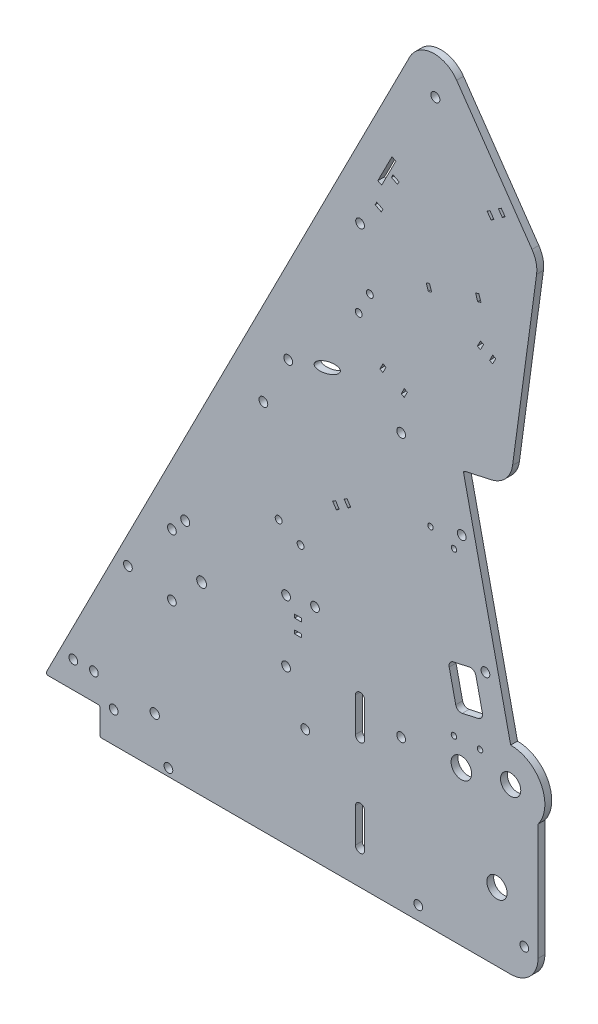
SolidWorks part; units mm, degrees
other "Markup1"
sketch "Sketch5"
ref_plane "Front Plane" through (0, 0, 0) normal (0, 0, 1) x (1, 0, 0)
ref_plane "Top Plane" through (0, 0, 0) normal (0, 1, 0) x (1, 0, 0)
ref_plane "Right Plane" through (0, 0, 0) normal (1, 0, 0) x (0, 0, -1)
sketch "Sketch1" plane through (0, 0, 0) normal (0, 0, 1) x (1, 0, 0)
  line L1 (228.6, -12.7) -> (228.6, 53.975)
  line L2 (178.7547, 351.4131) -> (0, 0)
  line L3 (228.6, 279.4) -> (178.7547, 351.4131)
  line L5 (0, 0) -> (25.4, 0)
  line L6 (25.4, 0) -> (25.4, -12.7)
  line L7 (25.4, -12.7) -> (228.6, -12.7)
  line L9 (215.9, 79.375) -> (193.9097, 178.5667)
  line L10 (193.9097, 178.5667) -> (215.6079, 183.377)
  line L11 (215.6079, 183.377) -> (228.6, 279.4)
  arc A0 (228.6, 53.975) -> (215.9, 79.375) centre (215.9, 63.5) ccw
  dimension "D7" = 12.7
  dimension "D8" = 76.2
  dimension "D10" = 31.75
  dimension "D2" = 292.1
  dimension "D3" = 25.4
  dimension "D4" = 215.9
  dimension "D5" = 394.2644
  dimension "D6" = 203.2
  dimension "D9" = 63.039
  dimension "D11" = 101.6
  dimension "D12" = 12.5
  dimension "D13" = 22.225
extrude "Boss-Extrude1" add sketch "Sketch1" along normal blind 3.175
sketch "Sketch2" plane through (0, 0, 3.175) normal (0, 0, 1) x (1, 0, 0)
  line L0 (178.7547, 351.4131) -> (0, 0) construction
  line L1 (25.4, -12.7) -> (228.6, -12.7) construction
  line L2 (215.9, 79.375) -> (193.9097, 178.5667) construction
  line L3 (193.9097, 178.5667) -> (215.6079, 183.377) construction
  line L4 (215.9, 79.375) -> (193.9097, 178.5667) construction
  line L5 (64.9432, 94.0578) -> (72.5445, 73.1732) construction
  line L6 (64.9432, 94.0578) -> (103.3734, 94.0578) construction
  line L10 (228.6, -12.7) -> (228.6, 53.975) construction
  circle A0 centre (64.9432, 94.0578) radius 2.0955
  circle A1 centre (180.975, 322.1643) radius 2.0955
  circle A2 centre (72.5445, 73.1732) radius 2.286
  circle A3 centre (193.2078, 152.3944) radius 2.032
  circle A4 centre (215.9, 63.5) radius 4.699
  circle A7 centre (173.0375, -6.35) radius 2.032
  circle A8 centre (204.203, 102.7985) radius 2.032
  circle A26 centre (209.55, 19.05) radius 4.699
  arc A30 (228.6, 53.975) -> (215.9, 79.375) centre (215.9, 63.5) ccw construction
  circle A31 centre (165.1, 179.3875) radius 2.032
  circle A35 centre (111.724, 87.4607) radius 2.032
  circle A36 centre (111.724, 58.8857) radius 2.032
  circle A37 centre (58.765, 58.8857) radius 2.032
  circle A38 centre (58.765, 87.4607) radius 2.032
  circle A39 centre (111.724, 58.8857) radius 1.905 construction
  circle A42 centre (111.724, 87.4607) radius 1.905 construction
  circle A43 centre (58.765, 58.8857) radius 1.905 construction
  circle A44 centre (58.765, 87.4607) radius 1.905 construction
  dimension "D3" = 4.191
  dimension "D5" = 4.191
  dimension "D9" = 4.572
  dimension "D20" = 9.398
  dimension "D23" = 9.398
  dimension "D18" = 4.064
  dimension "D26" = 4.064
  dimension "D14" = 4.064
  dimension "D10" = 4.064
  dimension "D2" = 15.24
  dimension "D6" = 15.24
  dimension "D7" = 22.225
  dimension "D21" = 44.45
  dimension "D22" = 6.35
  dimension "D19" = 160.3375
  dimension "D24" = 44.45
  dimension "D25" = 6.35
  dimension "D27" = 25.4
  dimension "D28" = 50.8
  dimension "D29" = 6.35
  dimension "D17" = 6.35
  dimension "D33" = 55.5625
  dimension "D15" = 114.3
  dimension "D4" = 180.975
  dimension "D8" = 70
extrude "Cut-Extrude1" cut sketch "Sketch2" against normal through all
sketch "Sketch7" plane through (0, 0, 3.175) normal (0, 0, 1) x (1, 0, 0)
  line L0 (146.05, 3.175) -> (146.05, 19.05) construction
  line L1 (143.891, 3.175) -> (143.891, 19.05)
  line L2 (148.209, 3.175) -> (148.209, 19.05)
  line L3 (146.05, 47.625) -> (146.05, 63.5) construction
  line L4 (143.891, 47.625) -> (143.891, 63.5)
  line L5 (148.209, 47.625) -> (148.209, 63.5)
  line L6 (25.4, -12.7) -> (228.6, -12.7) construction
  line L12 (228.6, -12.7) -> (228.6, 53.975) construction
  line L13 (25.4, -12.7) -> (228.6, -12.7) construction
  arc A0 (143.891, 3.175) -> (148.209, 3.175) centre (146.05, 3.175) ccw
  arc A1 (148.209, 19.05) -> (143.891, 19.05) centre (146.05, 19.05) ccw
  arc A2 (143.891, 47.625) -> (148.209, 47.625) centre (146.05, 47.625) ccw
  arc A3 (148.209, 63.5) -> (143.891, 63.5) centre (146.05, 63.5) ccw
  circle A8 centre (50.8, 9.525) radius 2.159
  point P2 (146.05, 11.1125)
  point P9 (146.05, 55.5625)
  dimension "D1" = 4.318
  dimension "D5" = 4.318
  dimension "D2" = 15.875
  dimension "D3" = 15.875
  dimension "D4" = 44.45
  dimension "D6" = 95.25
  dimension "D7" = 82.55
  dimension "D8" = 15.875
  dimension "D9" = 22.225
extrude "Cut-Extrude2" cut sketch "Sketch7" against normal through all
sketch "Sketch10" plane through (0, 0, 3.175) normal (0, 0, 1) x (1, 0, 0)
  circle A0 centre (120.65, 38.1) radius 2.032
  circle A1 centre (165.1, 57.15) radius 2.032
  circle A2 centre (13.0465, 12.3347) radius 2.032
  circle A3 centre (22.5715, 12.3347) radius 2.032
  circle A4 centre (38.3604, 62.564) radius 2.032
  circle A5 centre (13.0465, 12.3347) radius 2.032 construction
  circle A6 centre (22.5715, 12.3347) radius 2.032 construction
  dimension "D1" = 4.064
  dimension "D3" = 38.1
  dimension "D2" = 120.65
  dimension "D4" = 63.5
  dimension "D5" = 69.85
extrude "Cut-Extrude3" cut sketch "Sketch10" against normal up to next
fillet "Fillet1" radius 12.7 4 edges at (228.6, -12.7, 1.5875) (178.7547, 351.4131, 1.5875) (215.6079, 183.377, 1.5875) (228.6, 279.4, 1.5875)
fillet "Fillet2" radius 0.7937 4 edges at (25.4, -12.7, 1.5875) (25.4, 0, 1.5875) (193.9097, 178.5667, 1.5875) (0, 0, 1.5875)
sketch "Sketch12" plane through (0, 0, 3.175) normal (0, 0, 1) x (1, 0, 0)
  circle A0 centre (31.75, 1.5875) radius 2.032
  circle A1 centre (173.0375, -6.35) radius 2.032
  circle A2 centre (222.25, 1.5875) radius 2.032
  circle A3 centre (57.15, -9.2075) radius 2.032
  circle A4 centre (57.15, -9.2075) radius 2.286 construction
  dimension "D1" = 4.064
  dimension "D2" = 4.064
extrude "Cut-Extrude5" cut sketch "Sketch12" against normal through all
sketch "Sketch13" plane through (0, 0, 3.175) normal (0, 0, 1) x (1, 0, 0)
  line L1 (228.6, 0) -> (228.6, 53.975) construction
  line L2 (1.2943, 0) -> (24.6062, 0) construction
  line L3 (26.1937, -12.7) -> (215.9, -12.7) construction
  line L8 (178.2697, 245.9923) -> (176.7582, 245.5069)
  line L9 (179.2404, 242.9693) -> (178.2697, 245.9923)
  line L10 (177.7289, 242.4839) -> (179.2404, 242.9693)
  line L11 (176.7582, 245.5069) -> (177.7289, 242.4839)
  line L12 (178.2697, 245.9923) -> (176.7582, 245.5069)
  line L13 (179.2404, 242.9693) -> (178.2697, 245.9923)
  line L14 (177.7289, 242.4839) -> (179.2404, 242.9693)
  line L15 (176.7582, 245.5069) -> (177.7289, 242.4839)
  line L16 (160.8477, 288.1984) -> (154.2836, 275.294)
  line L17 (200.6096, 249.8308) -> (202.1211, 250.3161)
  line L18 (199.639, 252.8538) -> (200.6096, 249.8308)
  line L19 (201.1505, 253.3391) -> (199.639, 252.8538)
  line L20 (202.1211, 250.3161) -> (201.1505, 253.3391)
  line L21 (200.6096, 249.8308) -> (202.1211, 250.3161)
  line L22 (199.639, 252.8538) -> (200.6096, 249.8308)
  line L23 (201.1505, 253.3391) -> (199.639, 252.8538)
  line L24 (202.1211, 250.3161) -> (201.1505, 253.3391)
  line L25 (160.8477, 288.1984) -> (162.6303, 287.2917)
  line L26 (160.5905, 279.7801) -> (163.4204, 278.3406)
  line L27 (161.3102, 281.1951) -> (160.5905, 279.7801)
  line L28 (164.1402, 279.7556) -> (161.3102, 281.1951)
  line L29 (163.4204, 278.3406) -> (164.1402, 279.7556)
  line L30 (160.5905, 279.7801) -> (163.4204, 278.3406)
  line L31 (161.3102, 281.1951) -> (160.5905, 279.7801)
  line L32 (164.1402, 279.7556) -> (161.3102, 281.1951)
  line L33 (163.4204, 278.3406) -> (164.1402, 279.7556)
  line L34 (154.2836, 275.294) -> (156.0662, 274.3872)
  line L35 (162.6303, 287.2917) -> (156.0662, 274.3872)
  line L36 (153.7897, 266.4104) -> (153.0699, 264.9954)
  line L37 (156.6196, 264.9709) -> (153.7897, 266.4104)
  line L38 (155.8998, 263.5559) -> (156.6196, 264.9709)
  line L39 (153.0699, 264.9954) -> (155.8998, 263.5559)
  line L40 (153.7897, 266.4104) -> (153.0699, 264.9954)
  line L41 (156.6196, 264.9709) -> (153.7897, 266.4104)
  line L42 (155.8998, 263.5559) -> (156.6196, 264.9709)
  line L43 (153.0699, 264.9954) -> (155.8998, 263.5559)
  line L110 (153.9925, 274.7218) -> (157.3929, 281.4066) construction
  line L111 (155.7751, 273.815) -> (159.1755, 280.4999) construction
  line L122 (203.3303, 234.0299) -> (201.9154, 234.7497)
  line L123 (201.8908, 231.2) -> (203.3303, 234.0299)
  line L124 (200.4759, 231.9198) -> (201.8908, 231.2)
  line L125 (201.9154, 234.7497) -> (200.4759, 231.9198)
  line L126 (203.3303, 234.0299) -> (201.9154, 234.7497)
  line L127 (201.8908, 231.2) -> (203.3303, 234.0299)
  line L128 (200.4759, 231.9198) -> (201.8908, 231.2)
  line L129 (201.9154, 234.7497) -> (200.4759, 231.9198)
  line L130 (206.1357, 229.0407) -> (207.5507, 228.321)
  line L131 (207.5752, 231.8707) -> (206.1357, 229.0407)
  line L132 (208.9902, 231.1509) -> (207.5752, 231.8707)
  line L133 (207.5507, 228.321) -> (208.9902, 231.1509)
  line L134 (206.1357, 229.0407) -> (207.5507, 228.321)
  line L135 (207.5752, 231.8707) -> (206.1357, 229.0407)
  line L136 (208.9902, 231.1509) -> (207.5752, 231.8707)
  line L137 (207.5507, 228.321) -> (208.9902, 231.1509)
  line L138 (211.5405, 292.889) -> (210.2352, 291.9855)
  line L139 (213.3475, 290.2784) -> (211.5405, 292.889)
  line L140 (212.0422, 289.3749) -> (213.3475, 290.2784)
  line L141 (210.2352, 291.9855) -> (212.0422, 289.3749)
  line L142 (211.5405, 292.889) -> (210.2352, 291.9855)
  line L143 (213.3475, 290.2784) -> (211.5405, 292.889)
  line L144 (212.0422, 289.3749) -> (213.3475, 290.2784)
  line L145 (210.2352, 291.9855) -> (212.0422, 289.3749)
  line L146 (206.3193, 289.275) -> (205.014, 288.3715)
  line L147 (208.1263, 286.6644) -> (206.3193, 289.275)
  line L148 (206.821, 285.7609) -> (208.1263, 286.6644)
  line L149 (205.014, 288.3715) -> (206.821, 285.7609)
  line L150 (206.3193, 289.275) -> (205.014, 288.3715)
  line L151 (208.1263, 286.6644) -> (206.3193, 289.275)
  line L152 (206.821, 285.7609) -> (208.1263, 286.6644)
  line L153 (205.014, 288.3715) -> (206.821, 285.7609)
  line L184 (133.3504, 136.102) -> (135.0815, 133.4404)
  line L185 (133.3504, 136.102) -> (134.6812, 136.9675)
  line L186 (135.0815, 133.4404) -> (136.4123, 134.3059)
  line L187 (155.2281, 200.1197) -> (156.643, 199.3999)
  line L188 (156.6676, 202.9496) -> (155.2281, 200.1197)
  line L189 (158.0826, 202.2298) -> (156.6676, 202.9496)
  line L190 (156.643, 199.3999) -> (158.0826, 202.2298)
  line L191 (155.2281, 200.1197) -> (156.643, 199.3999)
  line L192 (156.6676, 202.9496) -> (155.2281, 200.1197)
  line L193 (158.0826, 202.2298) -> (156.6676, 202.9496)
  line L194 (156.643, 199.3999) -> (158.0826, 202.2298)
  line L195 (134.6812, 136.9675) -> (136.4123, 134.3059)
  line L196 (165.1328, 195.0814) -> (166.5478, 194.3617)
  line L197 (166.5723, 197.9113) -> (165.1328, 195.0814)
  line L198 (167.9873, 197.1916) -> (166.5723, 197.9113)
  line L199 (166.5478, 194.3617) -> (167.9873, 197.1916)
  line L200 (165.1328, 195.0814) -> (166.5478, 194.3617)
  line L201 (166.5723, 197.9113) -> (165.1328, 195.0814)
  line L202 (167.9873, 197.1916) -> (166.5723, 197.9113)
  line L203 (166.5478, 194.3617) -> (167.9873, 197.1916)
  line L204 (140.4047, 136.9025) -> (138.6737, 139.5641)
  line L205 (140.4047, 136.9025) -> (141.7355, 137.768)
  line L206 (138.6737, 139.5641) -> (140.0045, 140.4296)
  line L207 (141.7355, 137.768) -> (140.0045, 140.4296)
  line L209 (169.1053, 332.4434) -> (0.5868, 1.1536) construction
  line L210 (88.0466, 102.1523) -> (85.2167, 103.5918) construction
  line L288 (115.661, 81.8727) -> (118.836, 81.8727)
  line L289 (115.661, 81.8727) -> (115.661, 80.2852)
  line L290 (118.836, 81.8727) -> (118.836, 80.2852)
  line L291 (115.661, 80.2852) -> (118.836, 80.2852)
  line L292 (115.661, 75.5227) -> (118.836, 75.5227)
  line L293 (115.661, 75.5227) -> (115.661, 73.9352)
  line L294 (118.836, 75.5227) -> (118.836, 73.9352)
  line L295 (115.661, 73.9352) -> (118.836, 73.9352)
  line L297 (115.661, 86.2542) -> (115.661, 60.0922) construction
  line L298 (59.9715, 91.3977) -> (110.5175, 91.3977) construction
  circle A0 centre (112.7125, 182.5625) radius 2.032
  circle A1 centre (146.05, 254) radius 2.032
  circle A2 centre (101.1964, 159.9231) radius 2.032 construction
  circle A3 centre (101.1964, 159.9231) radius 2.032
  circle A4 centre (145.4254, 217.7376) radius 1.6 construction
  circle A5 centre (150.594, 227.8985) radius 1.6 construction
  circle A7 centre (145.4254, 217.7376) radius 1.6
  circle A8 centre (150.594, 227.8985) radius 1.6
  circle A9 centre (108.294, 116.1502) radius 1.6 construction
  circle A10 centre (118.455, 110.9816) radius 1.6 construction
  circle A11 centre (108.294, 116.1502) radius 1.6
  circle A12 centre (118.455, 110.9816) radius 1.6
  ellipse E0 centre (130.8261, 188.4615) end of major axis (136.864, 190.4279) minor radius 2.3812 construction
  ellipse E1 centre (130.8261, 188.4615) end of major axis (136.864, 190.4279) minor radius 2.3812
  dimension "D2" = 4.064
  dimension "D5" = 4.064
  dimension "D1" = 195.2625
  dimension "D3" = 82.55
  dimension "D4" = 254
  dimension "D6" = 115.8875
  dimension "D11" = 7.62
  dimension "D12" = 6.858
  dimension "D13" = 1.5875
  dimension "D14" = 3.175
  dimension "D15" = 4.7625
  dimension "D16" = 60
  dimension "D17" = 57.15
  dimension "D24" = 50.8
  dimension "D29" = 3.175
  dimension "D30" = 1.5875
  dimension "D31" = 4.7625
  dimension "D32" = 0
  dimension "D33" = 9.525
  dimension "D7" = 0
  dimension "D8" = 0
  dimension "D9" = 0
  dimension "D10" = 0
  dimension "D18" = 0
  dimension "D19" = 0
  dimension "D20" = 0
  dimension "D21" = 0
  dimension "D22" = 0
  dimension "D23" = 0
extrude "Cut-Extrude6" cut sketch "Sketch13" against normal through all
sketch "Sketch14" plane through (0, 0, 3.175) normal (0, 0, 1) x (1, 0, 0)
  line L5 (186.8444, 98.9502) -> (199.2434, 101.699)
  line L6 (186.8444, 98.9502) -> (190.9676, 80.3518)
  line L7 (190.9676, 80.3518) -> (203.3665, 83.1006)
  line L8 (199.2434, 101.699) -> (203.3665, 83.1006)
  line L14 (202.8168, 85.5804) -> (199.7931, 99.2192) construction
  line L15 (193.4474, 80.9015) -> (200.8868, 82.5508) construction
  line L16 (187.3942, 96.4704) -> (190.4178, 82.8316) construction
  line L17 (196.7636, 101.1493) -> (189.3242, 99.5) construction
  circle A0 centre (189.6022, 69.9806) radius 1.27
  circle A1 centre (201.7089, 70.5092) radius 1.27
  circle A2 centre (189.6022, 69.9806) radius 1.27 construction
  circle A3 centre (201.7089, 70.5092) radius 1.27 construction
  circle A4 centre (165.1, 57.15) radius 2.032
  circle A5 centre (125.1498, 89.5229) radius 2.032
  circle A6 centre (178.7216, 148.5324) radius 1.27
  circle A8 centre (178.7216, 148.5324) radius 1.27 construction
  circle A9 centre (189.6226, 145.0954) radius 1.27
  circle A10 centre (189.6226, 145.0954) radius 1.27 construction
  point P8 (152.4, 88.9)
  dimension "D1" = 4.064
extrude "Cut-Extrude7" cut sketch "Sketch14" against normal through all both and the other way through all
fillet "Fillet3" radius 2.54 4 edges at (199.2434, 101.699, 1.5875) (186.8444, 98.9502, 1.5875) (190.9676, 80.3518, 1.5875) (203.3665, 83.1006, 1.5875)
sketch "Sketch15" plane through (0, 0, 3.175) normal (0, 0, 1) x (1, 0, 0)
  circle A0 centre (193.04, 58.801) radius 4.7625 construction
  circle A1 centre (193.04, 58.801) radius 4.7625
extrude "Cut-Extrude8" cut sketch "Sketch15" against normal through all
equation "\"D6@Sketch2\"=\"D2@Sketch2\""
